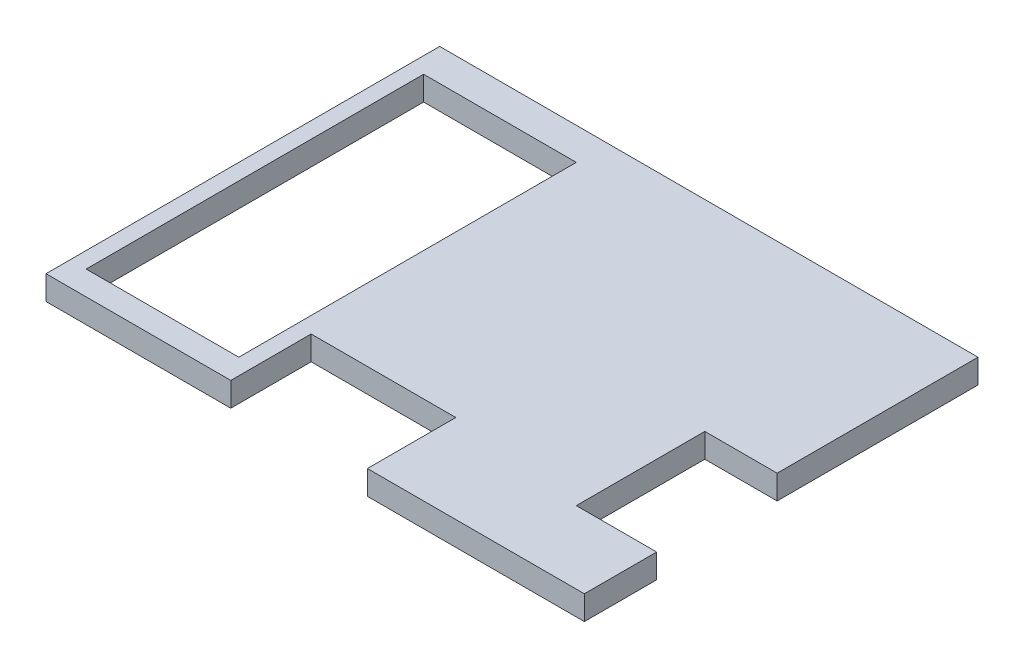
SolidWorks part; units mm, degrees
ref_plane "Front Plane" through (0, 0, 0) normal (0, 0, 1) x (1, 0, 0)
ref_plane "Top Plane" through (0, 0, 0) normal (0, 1, 0) x (1, 0, 0)
ref_plane "Right Plane" through (0, 0, 0) normal (1, 0, 0) x (0, 0, -1)
sketch "Sketch1" plane through (0, 0, 0) normal (0, 1, 0) x (1, 0, 0)
  line L0 (-33.4109, -24.4348) -> (-10.4109, -24.4348)
  line L1 (-33.4109, 24.5652) -> (33.5891, 24.5652)
  line L2 (-33.4109, 24.5652) -> (-33.4109, -24.4348)
  line L3 (7.5907, -25.4326) -> (34.5907, -25.4326)
  line L4 (33.5891, 24.5652) -> (33.5891, -0.4348)
  line L5 (-33.4109, 24.5652) -> (34.5907, -25.4326) construction
  line L6 (-33.4109, -24.4348) -> (33.5891, 24.5652) construction
  line L7 (-31.4109, 20.5652) -> (-12.4109, 20.5652)
  line L8 (-31.4109, 20.5652) -> (-31.4109, -21.4348)
  line L9 (-31.4109, -21.4348) -> (-12.4109, -21.4348)
  line L10 (-12.4109, 20.5652) -> (-12.4109, -21.4348)
  line L11 (-31.4109, 20.5652) -> (-12.4109, -21.4348) construction
  line L12 (-31.4109, -21.4348) -> (-12.4109, 20.5652) construction
  line L13 (34.5907, -16.4326) -> (34.5907, -25.4326)
  line L14 (7.5907, -25.4326) -> (7.5907, -14.4326)
  line L15 (7.5907, -14.4326) -> (-10.4109, -14.4326)
  line L16 (-10.4109, -24.4348) -> (-10.4109, -14.4326)
  line L17 (33.5891, -0.4348) -> (24.5891, -0.4348)
  line L19 (34.5907, -16.4326) -> (24.5891, -16.4326)
  line L20 (24.5891, -0.4348) -> (24.5891, -16.4326)
  point P0 (0, 0)
  point P6 (-21.9109, -0.4348)
  dimension "D1" = 67
  dimension "D2" = 49
  dimension "D3" = 25
  dimension "D4" = 4
  dimension "D5" = 2
  dimension "D6" = 19
  dimension "D7" = 23
  dimension "D8" = 9
  dimension "D9" = 9
  dimension "D10" = 27
  dimension "D11" = 11
extrude "Boss-Extrude1" add sketch "Sketch1" along normal blind 3
